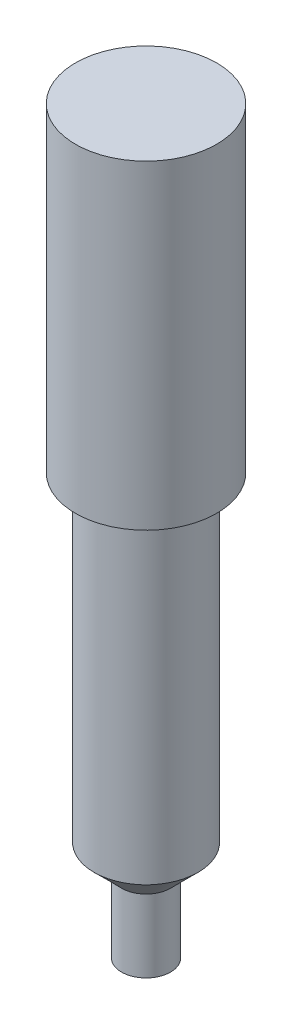
SolidWorks part; units mm, degrees
material "AISI 316 Annealed Stainless Steel Bar (SS)"
ref_plane "Front Plane" through (0, 0, 0) normal (0, 0, 1) x (1, 0, 0)
ref_plane "Top Plane" through (0, 0, 0) normal (0, 1, 0) x (1, 0, 0)
ref_plane "Right Plane" through (0, 0, 0) normal (1, 0, 0) x (0, 0, -1)
sketch "Sketch2" plane through (0, 0, 0) normal (0, 0, 1) x (1, 0, 0)
  line L0 (0, 0) -> (0, 508.8276) construction
  line L1 (0, 0) -> (6, 0)
  line L2 (0, 0) -> (0, 25.4)
  line L3 (0, 25.4) -> (6, 25.4)
  line L4 (6, 0) -> (6, 25.4)
  line L5 (0, 25.4) -> (12.721, 25.4)
  line L6 (0, 25.4) -> (0, 69.85)
  line L7 (0, 69.85) -> (12.721, 69.85)
  line L8 (12.721, 25.4) -> (12.721, 69.85)
  line L9 (0, 69.85) -> (12.721, 69.85)
  line L10 (0, 69.85) -> (0, 102.87)
  line L11 (0, 102.87) -> (12.721, 102.87)
  line L12 (12.721, 69.85) -> (12.721, 102.87)
  line L13 (0, 102.87) -> (17.272, 102.87)
  line L14 (0, 102.87) -> (0, 181.102)
  line L15 (0, 181.102) -> (17.272, 181.102)
  line L16 (17.272, 102.87) -> (17.272, 181.102)
  dimension "D1" = 78.232
  dimension "D2" = 17.272
  dimension "D4" = 33.02
  dimension "D3" = 12.721
  dimension "D5" = 44.45
  dimension "D6" = 12.721
  dimension "D7" = 25.4
  dimension "D8" = 6
revolve "Revolve1" add sketch "Sketch2" angle 360 about L0 region at (3, 12.7, 0) region at (6.3605, 47.625, 0) region at (6.3605, 86.36, 0) region at (8.636, 141.986, 0)
chamfer "Chamfer1" distance 7.62 angle 45 1 edges at (0, 25.4, -6)
equation "\"hole diamiter\"= 1.36in"
equation "\"wheel depth\"= 2.88"
equation "\"press_tolerance\"= 0.00165"
equation "\"wheel_connection\"= \"hole diamiter\"'https://at-machining.com/tolerance-press-fit/"
equation "\"D1@Sketch2\"=\"wheel depth\"+0.2"
equation "\"D2@Sketch2\"=\"wheel_connection\"/2"
equation "\"fitting depth\"= 1.3"
equation "\"D4@Sketch2\"=\"fitting depth\""
equation "\"bearing_id\"= 1"
equation "\"bearing_connection\"= \"bearing_id\" + \"press_tolerance\"'https://at-machining.com/tolerance-press-fit/"
equation "\"D3@Sketch2\"=\"bearing_connection\"/2"
equation "\"thread length\"= 1.75"
equation "\"major_diamiter\"= 0.9980'https://www.machiningdoctor.com/threadinfo/?tid=109"
equation "\"D5@Sketch2\"=\"thread length\""
equation "\"D6@Sketch2\"=\"bearing_connection\"/2"
equation "\"coupling diamiter\"= 12mm"
equation "\"coupling lenght\"=1"
equation "\"D7@Sketch2\"=\"coupling lenght\""
equation "\"D8@Sketch2\"=\"coupling diamiter\"/2"
